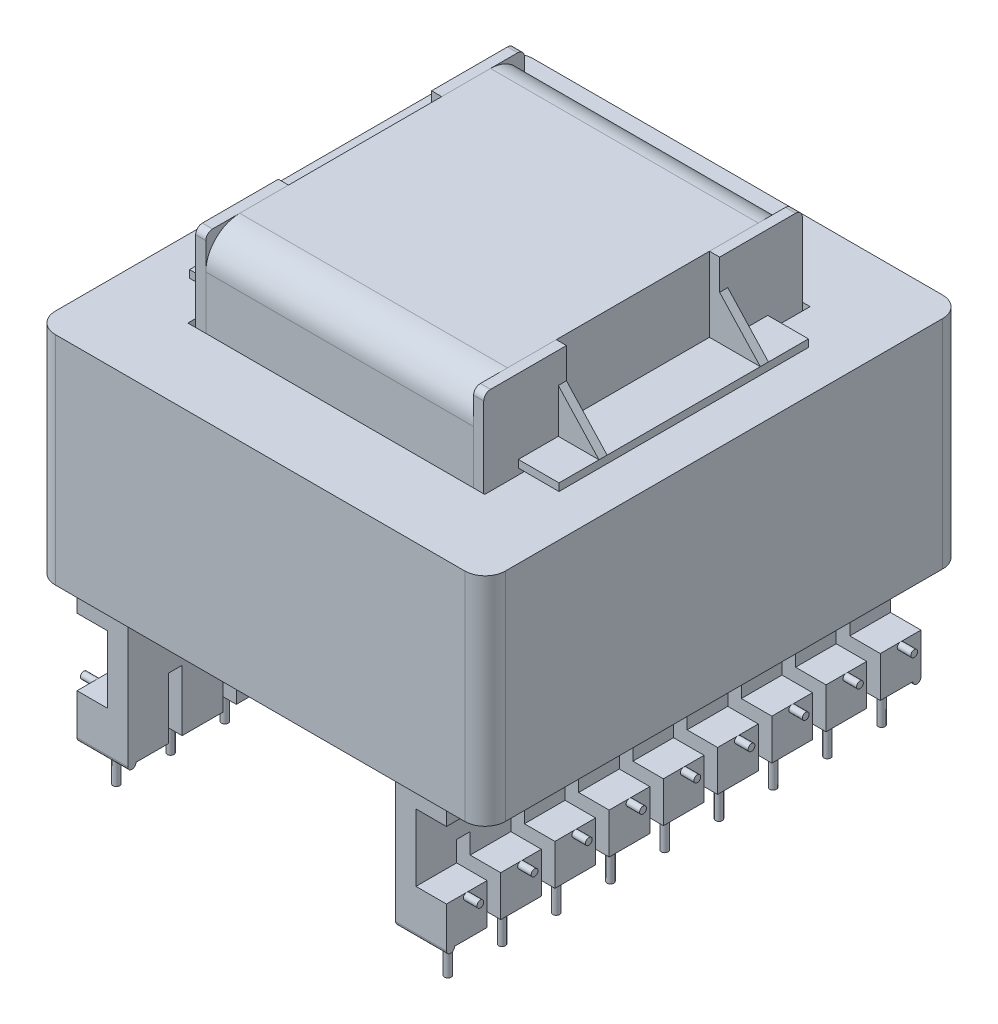
SolidWorks part; units mm, degrees
ref_plane "Спереди" through (0, 0, 0) normal (0, 0, 1) x (1, 0, 0)
ref_plane "Сверху" through (0, 0, 0) normal (0, 1, 0) x (1, 0, 0)
ref_plane "Справа" through (0, 0, 0) normal (1, 0, 0) x (0, 0, -1)
sketch "Эскиз1" plane through (0, 0, 0) normal (1, 0, 0) x (0, 0, -1)
  line L1 (-11.3, 16.25) -> (11.3, 16.25)
  line L2 (-11.3, 16.25) -> (-11.3, -16.25)
  line L3 (-11.3, -16.25) -> (11.3, -16.25)
  line L4 (11.3, 16.25) -> (11.3, -16.25)
  line L5 (-11.3, 16.25) -> (11.3, -16.25) construction
  line L6 (-11.3, -16.25) -> (11.3, 16.25) construction
  line L7 (-12.5, 17.35) -> (12.5, 17.35)
  line L8 (-12.5, 17.35) -> (-12.5, -17.35)
  line L9 (-12.5, -17.35) -> (12.5, -17.35)
  line L10 (12.5, 17.35) -> (12.5, -17.35)
  line L11 (-12.5, 17.35) -> (12.5, -17.35) construction
  line L12 (-12.5, -17.35) -> (12.5, 17.35) construction
  point P0 (0, 0)
  point P6 (0, 0)
  dimension "D1" = 22.6
  dimension "D2" = 32.5
  dimension "D3" = 25
  dimension "D4" = 34.7
extrude "Бобышка-Вытянуть1" add sketch "Эскиз1" along normal blind 19.75
sketch "Эскиз2" plane through (19.75, 0, 0) normal (1, 0, 0) x (0, 0, -1)
  line L0 (-12.5, -17.35) -> (12.5, -17.35) construction
  line L1 (11.3, -17.35) -> (23.5, -17.35)
  line L2 (11.3, -17.35) -> (11.3, 28.35)
  line L3 (11.3, 28.35) -> (22.5, 28.35)
  line L4 (23.5, -17.35) -> (23.5, 27.35)
  line L5 (11.3, 16.25) -> (-11.3, 16.25) construction
  line L6 (11.3, -16.25) -> (11.3, 16.25) construction
  line L7 (0, 0) -> (0, 38.0092) construction
  line L8 (-23.5, -17.35) -> (-23.5, 27.35)
  line L9 (-11.3, 28.35) -> (-22.5, 28.35)
  line L10 (-11.3, -17.35) -> (-11.3, 28.35)
  line L11 (-11.3, -17.35) -> (-23.5, -17.35)
  arc A0 (22.5, 28.35) -> (23.5, 27.35) centre (22.5, 27.35) cw
  arc A1 (-22.5, 28.35) -> (-23.5, 27.35) centre (-22.5, 27.35) ccw
  dimension "D3" = 1
  dimension "D1" = 23.5
  dimension "D2" = 12.1
extrude "Бобышка-Вытянуть2" add sketch "Эскиз2" along normal blind 1.5
sketch "Эскиз3" plane through (19.75, 0, 0) normal (1, 0, 0) x (0, 0, -1)
  line L0 (11.3, 16.25) -> (-11.3, 16.25) construction
  line L1 (18.4, 16.25) -> (-18.4, 16.25)
  line L2 (0, 16.25) -> (0, 17.35)
  line L3 (18.4, 17.35) -> (-18.4, 17.35)
  line L4 (-18.4, 16.25) -> (-18.4, 17.35)
  line L5 (11.3, 17.35) -> (-11.3, 17.35) construction
  line L6 (18.4, 16.25) -> (18.4, 17.35)
  line L7 (-11.3, -17.35) -> (11.3, -17.35) construction
  line L8 (-35, -17.35) -> (35, -17.35)
  line L9 (0, -17.35) -> (0, -16.25)
  line L10 (-35, -16.25) -> (35, -16.25)
  line L11 (35, -17.35) -> (35, -16.25)
  line L12 (-11.3, -16.25) -> (11.3, -16.25) construction
  line L13 (-35, -17.35) -> (-35, -16.25)
  dimension "D1" = 18.4
  dimension "D2" = 35
extrude "Бобышка-Вытянуть3" add sketch "Эскиз3" along normal blind 7.5 contours L1 L4 L3 L6 | L10 L11 L8 L13
sketch "Эскиз4" plane through (0, 17.35, 0) normal (0, 1, 0) x (1, 0, 0)
  line L0 (27.25, 18.4) -> (27.25, -18.4) construction
  line L1 (21.25, -11.3) -> (27.25, -11.3)
  line L2 (21.25, -11.3) -> (21.25, -12.5)
  line L3 (21.25, -12.5) -> (27.25, -12.5)
  line L4 (27.25, -11.3) -> (27.25, -12.5)
  line L5 (19.75, 12.5) -> (0, 12.5) construction
  line L6 (21.25, 11.3) -> (27.25, 11.3)
  line L7 (21.25, 11.3) -> (21.25, 12.5)
  line L8 (21.25, 12.5) -> (27.25, 12.5)
  line L9 (27.25, 11.3) -> (27.25, 12.5)
  line L10 (19.75, -12.5) -> (0, -12.5) construction
  point P16 (0, 0)
  point P17 (0, 0)
  point P18 (0, 0)
extrude "Бобышка-Вытянуть4" add sketch "Эскиз4" along normal blind 6.5 contours L8 L9 L6 L7 | L1 L4 L3 L2
sketch "Эскиз5" plane through (0, 0, -12.5) normal (0, 0, -1) x (-1, 0, 0)
  line L0 (-21.25, 23.85) -> (-27.25, 17.35)
  line L1 (-27.25, 17.35) -> (-27.25, 23.85)
  line L2 (-27.25, 23.85) -> (-21.25, 23.85)
  line L3 (-21.25, 23.85) -> (-21.2719, 23.84)
  line M3 (-21.25, 23.85) -> (-27.25, 23.85)
  line M4 (-27.25, 23.85) -> (-27.25, 17.35)
extrude "Вырез-Вытянуть1" cut sketch "Эскиз5" against normal through all contours L0 M3 M4 region at (25.25, 21.6833, -12.5)
sketch "Эскиз6" plane through (0, -17.35, 0) normal (0, -1, 0) x (-1, 0, 0)
  line L1 (-27.25, -35) -> (-19.75, -35)
  line L2 (-27.25, -35) -> (-27.25, 35)
  line L3 (-27.25, 35) -> (-19.75, 35)
  line L4 (-19.75, -35) -> (-19.75, 35)
extrude "Бобышка-Вытянуть5" add sketch "Эскиз6" along normal offset from surface (16.8 mm away) 62.5 up to face at (20.5, 28.35, -16.9)
sketch "Эскиз7" plane through (0, 0, -35) normal (0, 0, -1) x (-1, 0, 0)
  line L0 (-27.25, -34.15) -> (-27.25, -16.25) construction
  line L1 (-27.25, -28.15) -> (-22.75, -28.15)
  line L2 (-27.25, -28.15) -> (-27.25, -18.25)
  line L3 (-27.25, -18.25) -> (-22.75, -18.25)
  line L4 (-22.75, -28.15) -> (-22.75, -18.25)
  line L5 (-19.75, -34.15) -> (-19.75, -16.25) construction
  line L6 (-27.25, -16.25) -> (-19.75, -16.25) construction
  line L7 (-19.75, -34.15) -> (-27.25, -34.15) construction
  dimension "D1" = 3
  dimension "D2" = 2
  dimension "D3" = 6
extrude "Вырез-Вытянуть2" cut sketch "Эскиз7" against normal up to next
sketch "Эскиз9" plane through (0, -34.15, 0) normal (0, -1, 0) x (1, 0, 0)
  line L0 (0, 12.5) -> (0, -12.5) construction
  circle A0 centre (24.45, 32) radius 0.5
  circle A1 centre (24.45, 24) radius 0.5
  circle A2 centre (24.45, 16) radius 0.5
  circle A3 centre (24.45, 8) radius 0.5
  circle A4 centre (24.45, 0) radius 0.5
  circle A5 centre (24.45, -8) radius 0.5
  circle A6 centre (24.45, -16) radius 0.5
  circle A7 centre (24.45, -24) radius 0.5
  circle A8 centre (24.45, -32) radius 0.5
  dimension "D3" = 1
  dimension "D1" = 24.45
  dimension "D2" = 32
  dimension "D4" = 9
extrude "Бобышка-Вытянуть6" add sketch "Эскиз9" along normal blind 6
sketch "Эскиз10" plane through (27.25, 0, 0) normal (1, 0, 0) x (0, 0, -1)
  line L0 (35, -34.15) -> (-35, -34.15) construction
  line L1 (-29, -34.15) -> (-27, -34.15)
  line L2 (-29, -34.15) -> (-29, -25.15)
  line L3 (-29, -25.15) -> (-27, -25.15)
  line L4 (-27, -34.15) -> (-27, -25.15)
  line L5 (-35, -28.15) -> (35, -28.15) construction
  line L6 (-35, -34.15) -> (-35, -28.15) construction
  line L7 (-21, -34.15) -> (-19, -34.15)
  line L8 (-21, -34.15) -> (-21, -25.15)
  line L9 (-21, -25.15) -> (-19, -25.15)
  line L10 (-19, -34.15) -> (-19, -25.15)
  line L11 (-13, -34.15) -> (-11, -34.15)
  line L12 (-13, -34.15) -> (-13, -25.15)
  line L13 (-13, -25.15) -> (-11, -25.15)
  line L14 (-11, -34.15) -> (-11, -25.15)
  line L15 (-5, -34.15) -> (-3, -34.15)
  line L16 (-5, -34.15) -> (-5, -25.15)
  line L17 (-5, -25.15) -> (-3, -25.15)
  line L18 (-3, -34.15) -> (-3, -25.15)
  line L19 (3, -34.15) -> (5, -34.15)
  line L20 (3, -34.15) -> (3, -25.15)
  line L21 (3, -25.15) -> (5, -25.15)
  line L22 (5, -34.15) -> (5, -25.15)
  line L23 (11, -34.15) -> (13, -34.15)
  line L24 (11, -34.15) -> (11, -25.15)
  line L25 (11, -25.15) -> (13, -25.15)
  line L26 (13, -34.15) -> (13, -25.15)
  line L27 (19, -34.15) -> (21, -34.15)
  line L28 (19, -34.15) -> (19, -25.15)
  line L29 (19, -25.15) -> (21, -25.15)
  line L30 (21, -34.15) -> (21, -25.15)
  line L31 (27, -34.15) -> (29, -34.15)
  line L32 (27, -34.15) -> (27, -25.15)
  line L33 (27, -25.15) -> (29, -25.15)
  line L34 (29, -34.15) -> (29, -25.15)
  dimension "D1" = 3
  dimension "D2" = 6
  dimension "D3" = 2
  dimension "D4" = 8
extrude "Вырез-Вытянуть3" cut sketch "Эскиз10" against normal up to next
sketch "Эскиз11" plane through (27.25, 0, 0) normal (1, 0, 0) x (0, 0, -1)
  line L0 (-35, -28.15) -> (-29, -28.15) construction
  circle A0 centre (-32, -28.65) radius 0.5
  circle A1 centre (-24, -28.65) radius 0.5
  circle A2 centre (-16, -28.65) radius 0.5
  circle A3 centre (-8, -28.65) radius 0.5
  circle A4 centre (0, -28.65) radius 0.5
  circle A5 centre (8, -28.65) radius 0.5
  circle A6 centre (16, -28.65) radius 0.5
  circle A7 centre (24, -28.65) radius 0.5
  circle A8 centre (32, -28.65) radius 0.5
  point P2 (-32, -28.15)
  point P9 (-24, -28.15)
  point P13 (-16, -28.15)
  point P16 (-8, -28.15)
  point P19 (0, -28.15)
  point P22 (8, -28.15)
  point P25 (16, -28.15)
  point P28 (24, -28.15)
  point P31 (32, -28.15)
  dimension "D1" = 1
  dimension "D2" = 9
extrude "Бобышка-Вытянуть7" add sketch "Эскиз11" along normal blind 2
sketch "Эскиз13" plane through (27.25, 0, 0) normal (1, 0, 0) x (0, 0, -1)
  line L0 (-29, -34.15) -> (-35, -34.15) construction
  line L1 (-35, -34.15) -> (-33.8, -34.15)
  line L2 (0, -49.1553) -> (0, -4.971) construction
  line L3 (35, -34.15) -> (33.8, -34.15)
  arc A0 (-35, -34.15) -> (-33.8, -34.15) centre (-34.4, -34.15) ccw
  arc A1 (35, -34.15) -> (33.8, -34.15) centre (34.4, -34.15) cw
  dimension "D1" = 0.6
  dimension "D2" = 1.2
extrude "Бобышка-Вытянуть9" add sketch "Эскиз13" against normal up to surface (7.5 mm away) contours A1 L3 | A0 L1 up to face at (19.75, -17.5777, 0)
mirror "Зеркальное отражение1" of "Бобышка-Вытянуть9", "Бобышка-Вытянуть7", "Вырез-Вытянуть3", "Бобышка-Вытянуть6", "Вырез-Вытянуть2", "Бобышка-Вытянуть5", "Вырез-Вытянуть1", "Бобышка-Вытянуть3", "Бобышка-Вытянуть2", "Бобышка-Вытянуть1", "Бобышка-Вытянуть4"
sketch "Эскиз12" plane through (0, 0, -18.4) normal (0, 0, -1) x (-1, 0, 0)
  line L0 (21.25, 17.35) -> (27.25, 17.35)
  line L1 (27.25, 17.35) -> (21.25, 23.85)
  line L2 (21.25, 23.85) -> (21.25, 17.35)
  point P5 (0, 0)
  point P6 (21.25, 24.797)
  point P7 (21.25, 23.85)
extrude "Бобышка-Вытянуть8" add sketch "Эскиз12" against normal blind 1.5
sketch "Эскиз14" plane through (0, 0, 0) normal (1, 0, 0) x (0, 0, -1)
  line L0 (0, 0) -> (0, -16.25) construction
  line L1 (35.25, 16) -> (24, 16)
  line L2 (35.25, 16) -> (35.25, -16)
  line L3 (35.25, -16) -> (24, -16)
  line L4 (24, 16) -> (24, -16)
  line L5 (35.25, 16) -> (24, -16) construction
  line L6 (35.25, -16) -> (24, 16) construction
  line L7 (-35, -16.25) -> (35, -16.25) construction
  line L8 (-35.25, -16) -> (-24, 16) construction
  line L9 (-35.25, 16) -> (-24, -16) construction
  line L10 (-24, 16) -> (-24, -16)
  line L11 (-35.25, -16) -> (-24, -16)
  line L12 (-35.25, 16) -> (-35.25, -16)
  line L13 (-35.25, 16) -> (-24, 16)
  point P0 (29.625, 0)
  point P15 (-29.625, 0)
  dimension "D1" = 35.25
  dimension "D2" = 32
  dimension "D3" = 11.25
extrude "Бобышка-Вытянуть10" add sketch "Эскиз14" along normal blind 33.2 separate body
sketch "Эскиз15" plane through (33.2, 0, 0) normal (1, 0, 0) x (0, 0, -1)
  line L1 (24, -16) -> (-24, -16)
  line L2 (24, -16) -> (24, 16)
  line L3 (24, 16) -> (-24, 16)
  line L4 (-24, -16) -> (-24, 16)
  line L5 (24, -16) -> (-24, 16) construction
  line L6 (24, 16) -> (-24, -16) construction
  point P0 (0, 0)
extrude "Бобышка-Вытянуть11" add sketch "Эскиз15" against normal blind 11.3
sketch "Эскиз16" plane through (21.9, 0, 0) normal (-1, 0, 0) x (0, 0, 1)
  line L0 (24, -16) -> (-24, -16) construction
  line L1 (-11, 16) -> (11, 16)
  line L2 (-11, 16) -> (-11, -16)
  line L3 (-11, -16) -> (11, -16)
  line L4 (11, 16) -> (11, -16)
  line L5 (-11, 16) -> (11, -16) construction
  line L6 (-11, -16) -> (11, 16) construction
  point P0 (0, 0)
  dimension "D1" = 22
extrude "Бобышка-Вытянуть12" add sketch "Эскиз16" along normal blind 15.9
fillet "Скругление1" radius 3 2 edges at (33.2, 0, 35.25) (33.2, 0, -35.25)
mirror "Зеркальное отражение2" of "Бобышка-Вытянуть10", "Бобышка-Вытянуть11", "Бобышка-Вытянуть12", "Скругление1"
sketch "Эскиз17" plane through (-19.75, 0, 0) normal (1, 0, 0) x (0, 0, -1)
  line L0 (22.5, 28.35) -> (11.3, 28.35) construction
  line L1 (-12.5, -17.35) -> (12.5, -17.35)
  line L2 (-12.5, -17.35) -> (-12.5, 17.35)
  line L3 (-12.5, 17.35) -> (12.5, 17.35)
  line L4 (12.5, -17.35) -> (12.5, 17.35)
  line L5 (-12.5, -17.35) -> (12.5, 17.35) construction
  line L6 (-12.5, 17.35) -> (12.5, -17.35) construction
  line L7 (-18.5, -28.35) -> (18.5, -28.35)
  line L8 (-23.5, -23.35) -> (-23.5, 23.35)
  line L9 (-18.5, 28.35) -> (18.5, 28.35)
  line L10 (23.5, -23.35) -> (23.5, 23.35)
  line L11 (-23.5, -28.35) -> (23.5, 28.35) construction
  line L12 (-23.5, 28.35) -> (23.5, -28.35) construction
  line L13 (23.5, -16.25) -> (23.5, 27.35) construction
  arc A0 (-23.5, 23.35) -> (-18.5, 28.35) centre (-18.5, 23.35) cw
  arc A1 (-18.5, -28.35) -> (-23.5, -23.35) centre (-18.5, -23.35) cw
  arc A2 (18.5, -28.35) -> (23.5, -23.35) centre (18.5, -23.35) ccw
  arc A3 (18.5, 28.35) -> (23.5, 23.35) centre (18.5, 23.35) cw
  point P0 (0, 0)
  point P6 (0, 0)
  point P8 (0, 0)
  point P13 (24.1233, 28.8908)
  point P18 (0, 0)
  dimension "D1" = 5
extrude "Бобышка-Вытянуть14" add sketch "Эскиз17" along normal up to surface (39.5 mm away) separate body up to face at (19.75, -18.2382, 0)
